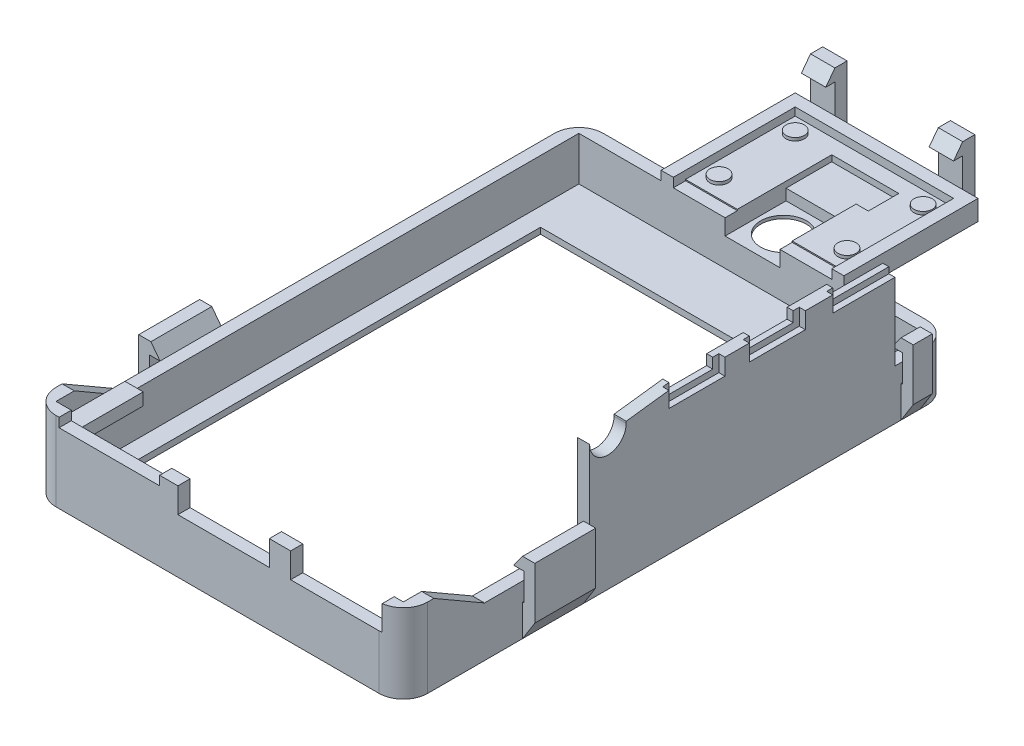
SolidWorks part; units mm, degrees
ref_plane "Płaszczyzna przednia" through (0, 0, 0) normal (0, 0, 1) x (1, 0, 0)
ref_plane "Płaszczyzna górna" through (0, 0, 0) normal (0, 1, 0) x (1, 0, 0)
ref_plane "Płaszczyzna prawa" through (0, 0, 0) normal (1, 0, 0) x (0, 0, -1)
sketch "Szkic2" plane through (0, 0, 0) normal (0, 1, 0) x (1, 0, 0)
  line L0 (-30.5, -40.9) -> (-25.5, -40.9) construction
  line L1 (-26.5, 44.9) -> (26.5, 44.9)
  line L2 (-30.5, 40.9) -> (-30.5, -40.9)
  line L3 (-26.5, -44.9) -> (26.5, -44.9)
  line L4 (30.5, 40.9) -> (30.5, -40.9)
  line L5 (-30.5, 44.9) -> (30.5, -44.9) construction
  line L6 (-30.5, -44.9) -> (30.5, 44.9) construction
  line L7 (-25.5, -41.9) -> (25.5, -41.9)
  line L8 (-25.5, -41.9) -> (-25.5, 33.6)
  line L9 (-25.5, 33.6) -> (25.5, 33.6)
  line L10 (25.5, -41.9) -> (25.5, 33.6)
  line L11 (25.5, -40.9) -> (30.5, -40.9) construction
  arc A0 (-30.5, -40.9) -> (-26.5, -44.9) centre (-26.5, -40.9) ccw
  arc A1 (26.5, -44.9) -> (30.5, -40.9) centre (26.5, -40.9) ccw
  arc A2 (26.5, 44.9) -> (30.5, 40.9) centre (26.5, 40.9) cw
  arc A3 (-26.5, 44.9) -> (-30.5, 40.9) centre (-26.5, 40.9) ccw
  point P0 (0, 0)
  point P18 (0, 0)
  dimension "D3" = 4
  dimension "D1" = 89.8
  dimension "D2" = 61
  dimension "D4" = 51
  dimension "D5" = 3
  dimension "D6" = 75.5
extrude "Dodanie-wyciągnięcie1" add sketch "Szkic2" along normal blind 1
sketch "Szkic3" plane through (0, 1, 0) normal (0, 1, 0) x (1, 0, 0)
  line L1 (-28.5, 42.9) -> (28.5, 42.9)
  line L2 (-28.5, 42.9) -> (-28.5, -42.9)
  line L3 (-28.5, -42.9) -> (28.5, -42.9)
  line L4 (28.5, 42.9) -> (28.5, -42.9)
  line L8 (-26.5, -44.9) -> (26.5, -44.9)
  line L9 (30.5, -40.9) -> (30.5, 40.9)
  line L10 (26.5, 44.9) -> (-26.5, 44.9)
  line L11 (-30.5, 40.9) -> (-30.5, -40.9)
  line L12 (-26.5, -44.9) -> (26.5, -44.9)
  line L13 (30.5, -40.9) -> (30.5, 40.9)
  line L14 (26.5, 44.9) -> (-26.5, 44.9)
  line L15 (-30.5, 40.9) -> (-30.5, -40.9)
  arc A4 (-30.5, -40.9) -> (-26.5, -44.9) centre (-26.5, -40.9) ccw
  arc A5 (26.5, -44.9) -> (30.5, -40.9) centre (26.5, -40.9) ccw
  arc A6 (30.5, 40.9) -> (26.5, 44.9) centre (26.5, 40.9) ccw
  arc A7 (-26.5, 44.9) -> (-30.5, 40.9) centre (-26.5, 40.9) ccw
  arc A8 (-30.5, -40.9) -> (-26.5, -44.9) centre (-26.5, -40.9) ccw
  arc A9 (26.5, -44.9) -> (30.5, -40.9) centre (26.5, -40.9) ccw
  arc A10 (30.5, 40.9) -> (26.5, 44.9) centre (26.5, 40.9) ccw
  arc A11 (-26.5, 44.9) -> (-30.5, 40.9) centre (-26.5, 40.9) ccw
  dimension "D2" = 2
  dimension "D3" = 2
  dimension "D4" = 2
  dimension "D5" = 2
  dimension "D1" = 0
extrude "Dodanie-wyciągnięcie2" add sketch "Szkic3" along normal blind 7.2
sketch "Szkic4" plane through (0, 8.2, 0) normal (0, 1, 0) x (1, 0, 0)
  line L0 (30.5, -40.9) -> (30.5, 40.9) construction
  line L1 (28.5, -42.9) -> (28.5, 42.9) construction
  line L2 (30.5, -14.33) -> (30.5, 35.77)
  line L3 (28.5, -14.33) -> (28.5, 35.77)
  line L4 (28.5, 35.77) -> (30.5, 35.77)
  line L5 (28.5, -14.33) -> (30.5, -14.33)
  line L6 (26.5, 44.9) -> (-26.5, 44.9) construction
  dimension "D1" = 50.1
  dimension "D2" = 9.13
extrude "Dodanie-wyciągnięcie3" add sketch "Szkic4" along normal blind 8
sketch "Szkic5" plane through (0, 0, 0) normal (0, -1, 0) x (1, 0, 0)
  line L0 (4.5, -44.9) -> (4.5, -42.9)
  line L1 (26.5, -44.9) -> (-26.5, -44.9) construction
  line L2 (4.5, -42.9) -> (-4.5, -42.9)
  line L3 (-4.5, -42.9) -> (-4.5, -44.9)
  line L4 (-4.5, -44.9) -> (4.5, -44.9)
  line L5 (-30.5, -40.9) -> (-30.5, -49.1859) construction
  line L6 (-4.5, -44.9) -> (-30.5, -44.9) construction
  line L7 (30.5, -40.9) -> (30.5, -54.2509) construction
  line L8 (4.5, -44.9) -> (30.5, -44.9) construction
  line L9 (30.5, 40.9) -> (30.5, -40.9) construction
  line L10 (-30.5, -40.9) -> (-30.5, 40.9) construction
  dimension "D1" = 9
  dimension "D2" = 2
extrude "Wytnij-wyciągnięcie1" cut sketch "Szkic5" against normal up to surface (8.2 mm away) up to face at (7.375, 8.2, -2.68)
sketch "Szkic8" plane through (0, 8.2, 0) normal (0, 1, 0) x (1, 0, 0)
  line L0 (30.5, -40.9) -> (30.5, -14.33) construction
  line L1 (28.5, -42.9) -> (28.5, -14.33) construction
  line L2 (-28.5, -42.9) -> (28.5, -42.9) construction
  line L3 (-28.5, 42.9) -> (-28.5, -42.9) construction
  line L4 (-30.5, 40.9) -> (-30.5, -40.9) construction
  line L5 (-26.5, -44.9) -> (26.5, -44.9) construction
  line L6 (30.5, -40.9) -> (30.5, -31.59)
  line L7 (28.5, -42.9) -> (28.5, -31.59)
  line L8 (-28.5, -42.9) -> (28.5, -42.9)
  line L9 (-28.5, -31.59) -> (-28.5, -42.9)
  line L10 (-30.5, -31.59) -> (-30.5, -40.9)
  line L11 (-26.5, -44.9) -> (26.5, -44.9)
  line L12 (30.5, -31.59) -> (28.5, -31.59)
  line L13 (-28.5, -31.59) -> (-30.5, -31.59)
  arc A0 (26.5, -44.9) -> (30.5, -40.9) centre (26.5, -40.9) ccw construction
  arc A1 (-30.5, -40.9) -> (-26.5, -44.9) centre (-26.5, -40.9) ccw construction
  arc A2 (26.5, -44.9) -> (30.5, -40.9) centre (26.5, -40.9) ccw
  arc A3 (-30.5, -40.9) -> (-26.5, -44.9) centre (-26.5, -40.9) ccw
  dimension "D1" = 13.31
extrude "Dodanie-wyciągnięcie5" add sketch "Szkic8" along normal blind 4.8
sketch "Szkic9" plane through (-30.5, 0, 0) normal (-1, 0, 0) x (0, 0, 1)
  line L0 (31.59, 13) -> (40.9, 13) construction
  line L1 (31.59, 13) -> (31.59, 8.2) construction
  line L2 (31.59, 13) -> (39.9038, 13)
  line L3 (31.59, 13) -> (31.59, 8.2)
  line L4 (31.59, 8.2) -> (39.9038, 13)
  line L5 (-40.9, 8.2) -> (31.59, 8.2) construction
  dimension "D1" = 150
extrude "Wytnij-wyciągnięcie3" cut sketch "Szkic9" against normal through all
sketch "Szkic10" plane through (0, 0, 44.9) normal (0, 0, 1) x (1, 0, 0)
  line L0 (-26, 13) -> (-26, 11.5)
  line L1 (-26.5, 13) -> (26.5, 13) construction
  line L2 (-26, 11.5) -> (-9.5, 11.5)
  line L3 (-9.5, 11.5) -> (-9.5, 13)
  line L4 (-6.5, 13) -> (-6.5, 8.9)
  line L5 (-6.5, 8.9) -> (8.5, 8.9)
  line L6 (8.5, 8.9) -> (8.5, 13)
  line L7 (12, 13) -> (12, 8.9)
  line L8 (12, 8.9) -> (27, 8.9)
  line L9 (27, 8.9) -> (27, 13)
  line L10 (27, 13) -> (12, 13)
  line L11 (8.5, 13) -> (-6.5, 13)
  line L12 (-9.5, 13) -> (-26, 13)
  line L13 (-30.5, 13) -> (-30.5, 0) construction
  point P16 (-9.5, 11.5)
  point P17 (-9.5, 13)
  point P18 (-26, 13)
  point P19 (-26, 11.5)
  point P20 (-6.5, 13)
  point P21 (-6.5, 8.9)
  point P22 (8.5, 8.9)
  dimension "D1" = 15
  dimension "D2" = 3.5
  dimension "D3" = 3
  dimension "D4" = 16.5
  dimension "D5" = 4.5
  dimension "D6" = 1.5
  dimension "D7" = 4.1
extrude "Wytnij-wyciągnięcie4" cut sketch "Szkic10" along direction (0, 0, -1) on the side against the normal up to surface (2 mm away) up to face at (0, 7, 42.9)
sketch "Szkic12" plane through (30.5, 0, 0) normal (1, 0, 0) x (0, 0, -1)
  line L0 (-14.33, 16.2) -> (-14.33, 22.1)
  line L2 (-14.33, 16.2) -> (35.77, 16.2) construction
  line L3 (-0.33, 23.4) -> (-0.33, 21.7)
  line L4 (-0.33, 21.7) -> (6.87, 21.7)
  line L5 (6.87, 21.7) -> (6.87, 23.4)
  line L6 (6.87, 23.4) -> (12.87, 23.4)
  line L7 (12.87, 23.4) -> (12.87, 21.7)
  line L8 (12.87, 21.7) -> (20.07, 21.7)
  line L9 (20.07, 21.7) -> (20.07, 23.4)
  line L10 (20.07, 23.4) -> (26.57, 23.4)
  line L11 (26.57, 23.4) -> (26.57, 21.8)
  line L12 (26.57, 21.8) -> (35.77, 21.8)
  line L13 (-0.33, 23.4) -> (6.87, 23.4) construction
  line L14 (-14.33, 16.2) -> (35.77, 16.2)
  line L15 (35.77, 21.8) -> (35.77, 16.2)
  line L16 (-14.33, 22.1) -> (-11.33, 22.1) construction
  line L17 (-0.33, 23.4) -> (-8.33, 22.4)
  line L18 (-8.33, 22.4) -> (-8.33, 22.1)
  arc A0 (-14.33, 22.1) -> (-8.33, 22.1) centre (-11.33, 22.1) ccw
  dimension "D2" = 6
  dimension "D1" = 6.2
  dimension "D3" = 7.2
  dimension "D4" = 8
  dimension "D5" = 9.2
  dimension "D6" = 6.5
  dimension "D7" = 6
  dimension "D8" = 5.6
  dimension "D9" = 5.5
  dimension "D10" = 0.3
extrude "Dodanie-wyciągnięcie7" add sketch "Szkic12" against normal up to surface (2 mm away) up to face at (28.5, 9.32, 2.8614)
sketch "Szkic11" plane through (-28.5, 0, 0) normal (1, 0, 0) x (0, 0, -1)
  line L1 (-31.59, 10.2) -> (-31.59, 8.2)
  line L2 (-31.59, 8.2) -> (-42.9, 8.2)
  line L3 (-42.9, 13) -> (-42.9, 1) construction
  line L8 (-42.9, 10.2) -> (-42.9, 8.2)
  line L9 (-42.9, 10.2) -> (-31.59, 10.2)
  dimension "D1" = 2
extrude "Dodanie-wyciągnięcie6" add sketch "Szkic11" along normal blind 3
sketch "Szkic13" plane through (0, 0, -44.9) normal (0, 0, -1) x (-1, 0, 0)
  line L0 (15, 8.2) -> (15, 9.7)
  line L1 (4.5, 8.2) -> (26.5, 8.2) construction
  line L2 (15, 9.7) -> (13, 9.7)
  line L3 (13, 9.7) -> (13, 8.4)
  line L4 (13, 8.4) -> (4.5, 8.4)
  line L5 (-13, 8.4) -> (-13, 9.7)
  line L6 (-13, 9.7) -> (-15, 9.7)
  line L7 (-15, 9.7) -> (-15, 8.2)
  line L8 (-26.5, 8.2) -> (-4.5, 8.2) construction
  line L9 (4.5, 8.2) -> (15, 8.2) construction
  line L10 (-4.5, 8.2) -> (-15, 8.2) construction
  line L11 (4.5, 8.4) -> (4.5, 8.2)
  line L12 (-13, 8.4) -> (-4.5, 8.4)
  line L13 (-4.5, 8.4) -> (-4.5, 8.2)
  line L14 (15, 8.2) -> (15, 6.4)
  line L15 (15, 6.4) -> (4.5, 6.4)
  line L16 (4.5, 8.2) -> (4.5, 0) construction
  line L17 (4.5, 6.4) -> (4.5, 8.2)
  line L18 (-4.5, 8.2) -> (-4.5, 6.4)
  line L19 (-4.5, 8.2) -> (-4.5, 0) construction
  line L20 (-4.5, 6.4) -> (-15, 6.4)
  line L21 (-15, 6.4) -> (-15, 8.2)
  dimension "D1" = 30
  dimension "D2" = 2
  dimension "D3" = 1.5
  dimension "D4" = 2
  dimension "D5" = 0.2
extrude "Dodanie-wyciągnięcie8" add sketch "Szkic13" along normal blind 20
sketch "Szkic14" plane through (-13, 0, 0) normal (1, 0, 0) x (0, 0, -1)
  line L0 (64.9, 8.4) -> (44.9, 8.4) construction
  line L1 (64.9, 9.7) -> (62.9, 9.7)
  line L2 (64.9, 9.7) -> (64.9, 8.4)
  line L3 (64.9, 8.4) -> (62.9, 8.4)
  line L4 (62.9, 9.7) -> (62.9, 8.4)
  dimension "D1" = 2
extrude "Dodanie-wyciągnięcie9" add sketch "Szkic14" along normal up to surface (8.5 mm away) up to face at (-4.5, 5.2222, -48.6778)
sketch "Szkic15" plane through (13, 0, 0) normal (-1, 0, 0) x (0, 0, 1)
  line L0 (-64.9, 8.4) -> (-44.9, 8.4) construction
  line L1 (-64.9, 9.7) -> (-62.9, 9.7)
  line L2 (-64.9, 9.7) -> (-64.9, 8.4)
  line L3 (-64.9, 8.4) -> (-62.9, 8.4)
  line L4 (-62.9, 9.7) -> (-62.9, 8.4)
  dimension "D1" = 2
extrude "Dodanie-wyciągnięcie10" add sketch "Szkic15" along normal up to surface (8.5 mm away) up to face at (4.5, 5.2222, -48.6778)
sketch "Szkic16" plane through (0, 8.4, 0) normal (0, 1, 0) x (1, 0, 0)
  line L0 (-10.5, 60.4) -> (-10.5, 62.9) construction
  line L1 (-4.5, 62.9) -> (-13, 62.9) construction
  line L2 (-10.5, 60.4) -> (-13, 60.4) construction
  line L3 (-13, 62.9) -> (-13, 44.9) construction
  line L4 (10.5, 60.4) -> (10.5, 62.9) construction
  line L5 (4.5, 62.9) -> (13, 62.9) construction
  line L6 (10.5, 60.4) -> (13, 60.4) construction
  line L8 (-10.5, 47.9) -> (-10.5, 60.4) construction
  line L9 (10.5, 47.9) -> (10.5, 60.4) construction
  line L10 (-10.5, 47.9) -> (10.5, 47.9) construction
  line L11 (-10.5, 60.4) -> (10.5, 60.4) construction
  line L12 (13, 62.9) -> (13, 44.9) construction
  circle A0 centre (-10.5, 60.4) radius 1.5
  circle A1 centre (-10.5, 47.9) radius 1.5
  circle A2 centre (10.5, 60.4) radius 1.5
  circle A3 centre (10.5, 47.9) radius 1.5
  dimension "D1" = 3
  dimension "D2" = 2.5
  dimension "D3" = 2.5
  dimension "D4" = 12.5
extrude "Dodanie-wyciągnięcie11" add sketch "Szkic16" along normal blind 0.5
sketch "Szkic18" plane through (0, 8.4, 0) normal (0, 1, 0) x (1, 0, 0)
  line L0 (4.5, 60.4) -> (6.5, 60.4)
  line L1 (4.5, 62.9) -> (4.5, 44.9) construction
  line L2 (6.5, 60.4) -> (6.5, 55.4)
  line L3 (6.5, 55.4) -> (4.5, 55.4)
  line L4 (4.5, 55.4) -> (4.5, 60.4)
  line L5 (4.5, 62.9) -> (13, 62.9) construction
  dimension "D1" = 2
  dimension "D2" = 5
  dimension "D3" = 2.5
extrude "Wytnij-wyciągnięcie6" cut sketch "Szkic18" against normal blind 1
sketch "Szkic20" plane through (0, 6.4, 0) normal (0, -1, 0) x (1, 0, 0)
  line L0 (4.5, -60.4) -> (-4.5, -60.4)
  line L1 (4.5, -64.9) -> (4.5, -44.9) construction
  line L2 (4.5, -55.4) -> (-4.5, -55.4)
  line L4 (-4.5, -64.9) -> (-4.5, -44.9) construction
  line L5 (4.5, -60.4) -> (4.5, -55.4)
  line L6 (-4.5, -60.4) -> (-4.5, -55.4)
  dimension "D1" = 5
extrude "Dodanie-wyciągnięcie12" add sketch "Szkic20" against normal up to surface (1 mm away) up to face at (5.5, 7.4, -57.9)
sketch "Szkic21" plane through (0, 6.4, 0) normal (0, -1, 0) x (-1, 0, 0)
  line L0 (4.5, 44.9) -> (4.5, 52.9)
  line L1 (4.5, 55.4) -> (4.5, 44.9) construction
  line L2 (4.5, 52.9) -> (-4.5, 52.9)
  line L3 (-4.5, 55.4) -> (-4.5, 44.9) construction
  line L4 (-4.5, 52.9) -> (-4.5, 44.9)
  line L5 (-4.5, 44.9) -> (-5.5, 44.9)
  line L6 (-15, 44.9) -> (-4.5, 44.9) construction
  line L7 (-5.5, 44.9) -> (-5.5, 53.9)
  line L8 (-5.5, 53.9) -> (5.5, 53.9)
  line L9 (5.5, 53.9) -> (5.5, 44.9)
  line L10 (4.5, 44.9) -> (15, 44.9) construction
  line L11 (5.5, 44.9) -> (4.5, 44.9) construction
  line L13 (0, 53.9) -> (0, 52.9) construction
  line L26 (4.5, 44.9) -> (15, 44.9)
  line L27 (15, 44.9) -> (15, 64.9)
  line L28 (15, 64.9) -> (4.5, 64.9)
  line L29 (4.5, 64.9) -> (4.5, 60.4)
  line L30 (4.5, 60.4) -> (-4.5, 60.4)
  line L31 (-4.5, 60.4) -> (-4.5, 64.9)
  line L32 (-4.5, 64.9) -> (-15, 64.9)
  line L33 (-15, 64.9) -> (-15, 44.9)
  line L34 (-15, 44.9) -> (-4.5, 44.9)
  line L35 (-4.5, 44.9) -> (-4.5, 55.4)
  line L36 (-4.5, 55.4) -> (4.5, 55.4)
  line L37 (4.5, 55.4) -> (4.5, 44.9)
  line L38 (4.5, 44.9) -> (5.5, 44.9)
  dimension "D1" = 8
  dimension "D2" = 1
  dimension "D3" = 0
extrude "Dodanie-wyciągnięcie13" add sketch "Szkic21" along normal blind 0.7
sketch "Szkic22" plane through (0, 5.7, 0) normal (0, -1, 0) x (1, 0, 0)
  line L0 (-4.5, -52.9) -> (-4.5, -53.9)
  line L1 (-5.5, -53.9) -> (5.5, -53.9) construction
  line L2 (-4.5, -52.9) -> (4.5, -52.9)
  line L3 (4.5, -52.9) -> (4.5, -53.9)
  line L4 (4.5, -53.9) -> (-4.5, -53.9)
extrude "Wytnij-wyciągnięcie7" cut sketch "Szkic22" against normal blind 0.7
sketch "Szkic23" plane through (-4.5, 0, 0) normal (1, 0, 0) x (0, 0, -1)
  line L0 (60.4, 7.4) -> (60.4, 8.4)
  line L1 (55.4, 7.4) -> (52.9, 7.4)
  line L2 (52.9, 7.4) -> (52.9, 5.7)
  line L17 (44.9, 0) -> (44.9, 5.7)
  line L18 (44.9, 5.7) -> (53.9, 5.7)
  line L19 (53.9, 5.7) -> (53.9, 6.4)
  line L20 (53.9, 6.4) -> (55.4, 6.4)
  line L21 (55.4, 6.4) -> (55.4, 7.4)
  line L22 (55.4, 7.4) -> (60.4, 7.4)
  line L23 (60.4, 7.4) -> (60.4, 6.4)
  line L24 (60.4, 6.4) -> (64.9, 6.4)
  line L25 (64.9, 6.4) -> (64.9, 9.7)
  line L26 (64.9, 9.7) -> (62.9, 9.7)
  line L27 (62.9, 9.7) -> (62.9, 8.4)
  line L28 (62.9, 8.4) -> (44.9, 8.4)
  line L29 (44.9, 8.4) -> (44.9, 8.2)
  line L30 (44.9, 8.2) -> (42.9, 8.2)
  line L31 (42.9, 8.2) -> (42.9, 1)
  line L32 (42.9, 1) -> (42.9, 0)
  line L33 (42.9, 0) -> (44.9, 0)
  line L35 (52.9, 5.7) -> (53.9, 5.7)
  line L36 (53.9, 5.7) -> (53.9, 6.4)
  line L37 (53.9, 6.4) -> (55.4, 6.4)
  line L38 (55.4, 6.4) -> (55.4, 7.4)
  line L40 (60.4, 7.4) -> (60.4, 6.4)
  line L41 (60.4, 6.4) -> (64.9, 6.4)
  line L42 (64.9, 6.4) -> (64.9, 9.7)
  line L43 (64.9, 9.7) -> (62.9, 9.7)
  line L44 (62.9, 9.7) -> (62.9, 8.4)
  line L45 (62.9, 8.4) -> (60.4, 8.4)
  point P8 (53.9, 6.05)
  dimension "D2" = 1
  dimension "D1" = 0
extrude "Dodanie-wyciągnięcie14" add sketch "Szkic23" along normal up to surface (9 mm away) up to face at (4.5, 5.4833, -48.525)
sketch "Szkic24" plane through (0, 0, -44.9) normal (0, 0, 1) x (1, 0, 0)
  line L0 (13, 8.4) -> (13, 8.2)
  line L1 (-13, 8.4) -> (-13, 8.2)
  line L6 (-15, 9.7) -> (-15, 8.2)
  line L7 (-15, 8.2) -> (-4.5, 8.2)
  line L8 (-4.5, 8.2) -> (-4.5, 8.4)
  line L9 (-4.5, 8.4) -> (-13, 8.4)
  line L10 (-13, 8.4) -> (-13, 9.7)
  line L11 (-13, 9.7) -> (-15, 9.7)
  line L12 (-15, 9.7) -> (-15, 8.2)
  line L13 (-15, 8.2) -> (-13, 8.2)
  line L16 (-13, 8.4) -> (-13, 9.7)
  line L17 (-13, 9.7) -> (-15, 9.7)
  line L18 (4.5, 8.4) -> (4.5, 8.2)
  line L19 (4.5, 8.2) -> (15, 8.2)
  line L20 (15, 8.2) -> (15, 9.7)
  line L21 (15, 9.7) -> (13, 9.7)
  line L22 (13, 9.7) -> (13, 8.4)
  line L25 (13, 8.2) -> (15, 8.2)
  line L26 (15, 8.2) -> (15, 9.7)
  line L28 (13, 9.7) -> (13, 8.4)
  line L32 (15, 9.7) -> (13, 9.7)
  line L33 (13, 8.4) -> (4.5, 8.4)
  dimension "D1" = 0
  dimension "D2" = 0
extrude "Dodanie-wyciągnięcie15" add sketch "Szkic24" along normal up to surface (2 mm away) up to face at (16.5, 4.6, -42.9)
sketch "Szkic25" plane through (30.5, 0, 0) normal (1, 0, 0) x (0, 0, -1)
  line L0 (-31.59, 8.2) -> (-14.33, 8.2) construction
  line L1 (-15.33, 8.2) -> (-25.33, 8.2)
  line L2 (-15.33, 8.2) -> (-15.33, 6.2)
  line L3 (-15.33, 6.2) -> (-25.33, 6.2)
  line L4 (-25.33, 8.2) -> (-25.33, 6.2)
  line L5 (-14.33, 22.1) -> (-14.33, 8.2) construction
  dimension "D1" = 1
  dimension "D2" = 10
  dimension "D3" = 2
extrude "Dodanie-wyciągnięcie16" add sketch "Szkic25" along normal blind 2
sketch "Szkic26" plane through (0, 8.2, 0) normal (0, 1, 0) x (1, 0, 0)
  line L1 (32.5, -15.33) -> (30.5, -15.33)
  line L2 (32.5, -15.33) -> (32.5, -25.33)
  line L3 (32.5, -25.33) -> (30.5, -25.33)
  line L4 (30.5, -15.33) -> (30.5, -25.33)
extrude "Dodanie-wyciągnięcie17" add sketch "Szkic26" along normal blind 3.5
sketch "Szkic27" plane through (0, 0, 25.33) normal (0, 0, 1) x (1, 0, 0)
  line L0 (30.5, 11.7) -> (30.5, 9.7)
  line L1 (30.5, 11.7) -> (30.5, 8.2) construction
  line L2 (30.5, 9.7) -> (29, 9.7)
  line L3 (29, 9.7) -> (30.5, 11.7)
  line L4 (30.5, 8.2) -> (28.5, 8.2) construction
  dimension "D1" = 1.5
  dimension "D2" = 1.5
extrude "Dodanie-wyciągnięcie18" add sketch "Szkic27" against normal up to surface (10 mm away) up to face at (31.3, 8.8, 15.33)
sketch "Szkic28" plane through (30.5, 0, 0) normal (1, 0, 0) x (0, 0, -1)
  line L0 (-25.33, 11.7) -> (-15.33, 11.7) construction
  line L1 (39.9, 6.2) -> (36.77, 6.2)
  line L2 (39.9, 6.2) -> (39.9, 11.7)
  line L3 (39.9, 11.7) -> (36.77, 11.7)
  line L4 (36.77, 6.2) -> (36.77, 11.7)
  line L5 (-25.33, 6.2) -> (-15.33, 6.2) construction
  line L6 (35.77, 21.8) -> (35.77, 8.2) construction
  line L7 (40.9, 8.2) -> (40.9, 0) construction
  dimension "D1" = 1
  dimension "D2" = 1
extrude "Dodanie-wyciągnięcie19" add sketch "Szkic28" along normal blind 1
sketch "Szkic29" plane through (0, 0, -39.9) normal (0, 0, -1) x (-1, 0, 0)
  line L0 (-30.5, 11.7) -> (-30.5, 9.7)
  line L7 (-30.5, 6.2) -> (-30.5, 8.2)
  line L8 (-30.5, 8.2) -> (-30.5, 9.7)
  line L9 (-30.5, 9.7) -> (-29, 9.7)
  line L10 (-29, 9.7) -> (-30.5, 11.7)
  line L11 (-30.5, 11.7) -> (-32.5, 11.7)
  line L12 (-32.5, 11.7) -> (-32.5, 6.2)
  line L13 (-32.5, 6.2) -> (-30.5, 6.2)
  line L16 (-30.5, 9.7) -> (-29, 9.7)
  line L17 (-29, 9.7) -> (-30.5, 11.7)
  dimension "D1" = 0
extrude "Dodanie-wyciągnięcie20" add sketch "Szkic29" against normal up to surface (3.13 mm away) up to face at (30.9, 8.8, -36.77)
sketch "Szkic30" plane through (0, 0, -64.9) normal (0, 0, -1) x (-1, 0, 0)
  line L0 (-15, 6.4) -> (15, 6.4) construction
  line L1 (12.4832, 6.4) -> (8.4832, 6.4)
  line L2 (12.4832, 6.4) -> (12.4832, 16.5)
  line L3 (12.4832, 16.5) -> (8.4832, 16.5)
  line L4 (8.4832, 6.4) -> (8.4832, 16.5)
  line L5 (-8.4832, 6.4) -> (-12.4832, 6.4)
  line L6 (-8.4832, 6.4) -> (-8.4832, 16.5)
  line L7 (-8.4832, 16.5) -> (-12.4832, 16.5)
  line L8 (-12.4832, 6.4) -> (-12.4832, 16.5)
  line L9 (12.4832, 6.4) -> (15, 6.4) construction
  line L10 (-12.4832, 6.4) -> (-15, 6.4) construction
  line L11 (15, 9.7) -> (-15, 9.7) construction
  dimension "D1" = 4
  dimension "D2" = 6.8
extrude "Dodanie-wyciągnięcie21" add sketch "Szkic30" along normal blind 2
sketch "Szkic32" plane through (12.4832, 0, 0) normal (1, 0, 0) x (0, 0, -1)
  line L0 (64.9, 16.5) -> (63.4, 14.5)
  line L1 (63.4, 14.5) -> (64.9, 14.5)
  line L2 (64.9, 16.5) -> (64.9, 9.7) construction
  line L3 (64.9, 14.5) -> (64.9, 16.5)
  dimension "D1" = 2
  dimension "D2" = 1.5
extrude "Dodanie-wyciągnięcie22" add sketch "Szkic32" against normal up to surface (24.9664 mm away) up to face at (-12.4832, 11.1, -65.7)
sketch "Szkic33" plane through (0, 0, -64.9) normal (0, 0, -1) x (-1, 0, 0)
  line L4 (8.4832, 14.5) -> (8.4832, 16.5)
  line L5 (8.4832, 16.5) -> (-8.4832, 16.5)
  line L6 (-8.4832, 16.5) -> (-8.4832, 14.5)
  line L7 (-8.4832, 14.5) -> (8.4832, 14.5)
  line L8 (8.4832, 14.5) -> (8.4832, 16.5)
  line L9 (8.4832, 16.5) -> (-8.4832, 16.5)
  line L10 (-8.4832, 16.5) -> (-8.4832, 14.5)
  line L11 (-8.4832, 14.5) -> (8.4832, 14.5)
  dimension "D1" = 0
extrude "Wytnij-wyciągnięcie8" cut sketch "Szkic33" against normal up to surface up to face at (0, 15.8333, -64.4)
sketch "Szkic34" plane through (0, 6.2, 0) normal (0, -1, 0) x (1, 0, 0)
  line L4 (30.5, 25.33) -> (30.5, 15.33)
  line L5 (30.5, 15.33) -> (32.5, 15.33)
  line L6 (32.5, 15.33) -> (32.5, 25.33)
  line L7 (32.5, 25.33) -> (30.5, 25.33)
  line L8 (30.5, 25.33) -> (30.5, 15.33)
  line L9 (30.5, 15.33) -> (32.5, 15.33)
  line L10 (32.5, 15.33) -> (32.5, 25.33)
  line L11 (32.5, 25.33) -> (30.5, 25.33)
  line L12 (30.5, -36.77) -> (30.5, -39.9)
  line L13 (30.5, -39.9) -> (31.5, -39.9)
  line L14 (31.5, -39.9) -> (31.5, -36.77)
  line L15 (31.5, -36.77) -> (30.5, -36.77)
  line L16 (30.5, -36.77) -> (30.5, -39.9)
  line L17 (30.5, -39.9) -> (31.5, -39.9)
  line L18 (31.5, -39.9) -> (31.5, -36.77)
  line L19 (31.5, -36.77) -> (30.5, -36.77)
  dimension "D1" = 0
  dimension "D2" = 0
extrude "Dodanie-wyciągnięcie23" add sketch "Szkic34" along normal blind 3
sketch "Szkic35" plane through (0, 0, -39.9) normal (0, 0, -1) x (-1, 0, 0)
  line L0 (-30.5, 9.7) -> (-30.7, 9.7)
  line L1 (-30.7, 9.7) -> (-30.7, 5.2)
  line L2 (-30.7, 5.2) -> (-30.5, 5.2)
  line L3 (-30.5, 3.2) -> (-31.5, 3.2) construction
  line L7 (-30.5, 3.2) -> (-30.5, 8.2)
  line L8 (-30.5, 8.2) -> (-30.5, 9.7)
  line L9 (-30.5, 9.7) -> (-29, 9.7)
  line L10 (-29, 9.7) -> (-30.5, 11.7)
  line L11 (-30.5, 11.7) -> (-31.5, 11.7)
  line L12 (-31.5, 11.7) -> (-31.5, 3.2)
  line L13 (-31.5, 3.2) -> (-30.5, 3.2)
  line L14 (-30.5, 5.2) -> (-30.5, 8.2)
  line L15 (-30.5, 8.2) -> (-30.5, 9.7)
  dimension "D2" = 0.2
  dimension "D3" = 2
  dimension "D1" = 0
extrude "Wytnij-wyciągnięcie9" cut sketch "Szkic35" against normal through all
sketch "Szkic36" plane through (31.5, 0, 0) normal (1, 0, 0) x (0, 0, -1)
  line L4 (39.9, 3.2) -> (39.9, 11.7)
  line L5 (39.9, 11.7) -> (36.77, 11.7)
  line L6 (36.77, 11.7) -> (36.77, 3.2)
  line L7 (36.77, 3.2) -> (39.9, 3.2)
  line L8 (39.9, 3.2) -> (39.9, 11.7)
  line L9 (39.9, 11.7) -> (36.77, 11.7)
  line L10 (36.77, 11.7) -> (36.77, 3.2)
  line L11 (36.77, 3.2) -> (39.9, 3.2)
  dimension "D1" = 0
extrude "Dodanie-wyciągnięcie24" add sketch "Szkic36" along normal up to surface (1 mm away) up to face at (32.5, 7.45, 20.33)
sketch "Szkic38" plane through (0, 5.7, 0) normal (0, -1, 0) x (1, 0, 0)
  line L8 (-5.5, -53.9) -> (5.5, -53.9)
  line L9 (5.5, -53.9) -> (5.5, -44.9)
  line L10 (5.5, -44.9) -> (4.5, -44.9)
  line L11 (4.5, -44.9) -> (4.5, -52.9)
  line L12 (4.5, -52.9) -> (-4.5, -52.9)
  line L13 (-4.5, -52.9) -> (-4.5, -44.9)
  line L14 (-4.5, -44.9) -> (-5.5, -44.9)
  line L15 (-5.5, -44.9) -> (-5.5, -53.9)
  line L16 (-5.5, -53.9) -> (5.5, -53.9)
  line L17 (5.5, -53.9) -> (5.5, -44.9)
  line L18 (5.5, -44.9) -> (4.5, -44.9)
  line L19 (4.5, -44.9) -> (4.5, -52.9)
  line L20 (4.5, -52.9) -> (-4.5, -52.9)
  line L21 (-4.5, -52.9) -> (-4.5, -44.9)
  line L22 (-4.5, -44.9) -> (-5.5, -44.9)
  line L23 (-5.5, -44.9) -> (-5.5, -53.9)
  dimension "D1" = 0
extrude "Dodanie-wyciągnięcie25" add sketch "Szkic38" along normal blind 0.6
sketch "Szkic39" plane through (-4.5, 0, 0) normal (1, 0, 0) x (0, 0, -1)
  line L0 (42.9, 5.1) -> (42.9, 5.6)
  line L1 (42.9, 5.6) -> (52.9, 5.6)
  line L2 (52.9, 7.4) -> (52.9, 5.1) construction
  line L3 (52.9, 5.6) -> (52.9, 5.1)
  line L4 (52.9, 5.1) -> (42.9, 5.1)
  line L5 (42.9, 8.2) -> (42.9, 1) construction
  dimension "D1" = 0.5
extrude "Dodanie-wyciągnięcie26" add sketch "Szkic39" along normal up to surface (9 mm away) up to face at (4.5, 5.3818, -47.7182)
sketch "Szkic41" plane through (0, 5.1, 0) normal (0, -1, 0) x (1, 0, 0)
  line L0 (0, -51.75) -> (0, -53.5) construction
  line L1 (0, -53.5) -> (0, -53.9) construction
  line L2 (-5.5, -53.9) -> (5.5, -53.9) construction
  line L3 (-3.75, -48) -> (-5.5, -48) construction
  line L4 (-5.5, -44.9) -> (-5.5, -53.9) construction
  line L5 (3.75, -48) -> (5.5, -48) construction
  line L6 (5.5, -53.9) -> (5.5, -44.9) construction
  circle A0 centre (0, -48) radius 3.75
  dimension "D1" = 7.5
  dimension "D2" = 0.4
extrude "Wytnij-wyciągnięcie10" cut sketch "Szkic41" against normal up to surface (0.5 mm away) up to face at (0, 5.6, -47.9)
mirror "Lustro3" about plane through (0, 0, 0) normal (1, 0, 0) of "Wytnij-wyciągnięcie9", "Dodanie-wyciągnięcie23", "Dodanie-wyciągnięcie16", "Dodanie-wyciągnięcie17", "Dodanie-wyciągnięcie18"
sketch "Szkic42" plane through (-31.5, 0, 0) normal (-1, 0, 0) x (0, 0, 1)
  line L4 (-36.77, 6.2) -> (-39.9, 6.2)
  line L5 (-39.9, 6.2) -> (-39.9, 3.2)
  line L6 (-39.9, 3.2) -> (-36.77, 3.2)
  line L7 (-36.77, 3.2) -> (-36.77, 6.2)
  line L8 (-36.77, 6.2) -> (-39.9, 6.2)
  line L9 (-39.9, 6.2) -> (-39.9, 3.2)
  line L10 (-39.9, 3.2) -> (-36.77, 3.2)
  line L11 (-36.77, 3.2) -> (-36.77, 6.2)
  dimension "D1" = 0
extrude "Wytnij-wyciągnięcie11" cut sketch "Szkic42" against normal up to surface (1 mm away) up to face at (-30.5, 4.2, 20.33)
sketch "Szkic43" plane through (30.5, 0, 0) normal (1, 0, 0) x (0, 0, -1)
  line L0 (35.77, 20.8) -> (25.57, 20.8)
  line L1 (35.77, 21.8) -> (35.77, 8.2) construction
  line L2 (25.57, 20.8) -> (25.57, 23.4)
  line L3 (26.57, 23.4) -> (20.07, 23.4) construction
  line L4 (25.57, 23.4) -> (26.57, 23.4)
  line L5 (26.57, 23.4) -> (26.57, 21.8)
  line L6 (26.57, 21.8) -> (35.77, 21.8)
  line L7 (35.77, 21.8) -> (35.77, 20.8)
  line L8 (21.07, 23.4) -> (21.07, 20.7)
  line L9 (21.07, 20.7) -> (11.87, 20.7)
  line L10 (11.87, 20.7) -> (11.87, 23.4)
  line L11 (12.87, 23.4) -> (6.87, 23.4) construction
  line L12 (11.87, 23.4) -> (12.87, 23.4)
  line L13 (12.87, 23.4) -> (12.87, 21.7)
  line L14 (12.87, 21.7) -> (20.07, 21.7)
  line L15 (20.07, 21.7) -> (20.07, 23.4)
  line L16 (20.07, 23.4) -> (20.07, 21.7) construction
  line L17 (20.07, 23.4) -> (21.07, 23.4)
  line L18 (6.87, 23.4) -> (7.87, 23.4)
  line L19 (7.87, 23.4) -> (7.87, 20.7)
  line L20 (7.87, 20.7) -> (-1.33, 20.7)
  line L21 (-1.33, 20.7) -> (-1.33, 23.275)
  line L22 (-0.33, 23.4) -> (-8.33, 22.4) construction
  line L23 (-1.33, 23.275) -> (-0.33, 23.4)
  line L24 (-0.33, 23.4) -> (-0.33, 21.7)
  line L25 (-0.33, 21.7) -> (6.87, 21.7)
  line L26 (6.87, 21.7) -> (-0.33, 21.7) construction
  line L27 (6.87, 21.7) -> (6.87, 23.4)
  line L28 (-1.33, 23.275) -> (-0.33, 23.275) construction
  dimension "D1" = 1
  dimension "D2" = 1
extrude "Wytnij-wyciągnięcie12" cut sketch "Szkic43" against normal blind 1
sketch "Szkic44" plane through (0, 0, 25.33) normal (0, 0, 1) x (1, 0, 0)
  line L0 (32.5, 3.2) -> (30.5, 3.2)
  line L1 (30.5, 3.2) -> (30.5, 0)
  line L2 (30.5, 0) -> (32.5, 3.2)
  point P5 (0, 0)
  point P6 (0, 0)
  point P7 (30.5, 0)
  point P10 (30.5, 0)
extrude "Dodanie-wyciągnięcie27" add sketch "Szkic44" against normal up to surface (65.23 mm away) up to face at (30.8625, 7.45, -39.9)
sketch "Szkic45" plane through (0, 3.2, 0) normal (0, 1, 0) x (1, 0, 0)
  line L4 (30.5, -15.33) -> (32.5, -15.33)
  line L5 (32.5, -15.33) -> (32.5, 36.77)
  line L6 (32.5, 36.77) -> (30.5, 36.77)
  line L7 (30.5, 36.77) -> (30.5, -15.33)
  line L8 (30.5, -15.33) -> (32.5, -15.33)
  line L9 (32.5, -15.33) -> (32.5, 36.77)
  line L10 (32.5, 36.77) -> (30.5, 36.77)
  line L11 (30.5, 36.77) -> (30.5, -15.33)
  dimension "D1" = 0
extrude "Wytnij-wyciągnięcie13" cut sketch "Szkic45" against normal up to surface up to face at (31.8333, 2.1333, -8.43)
sketch "Szkic46" plane through (0, 0, 15.33) normal (0, 0, -1) x (-1, 0, 0)
  line L0 (32.5, 3.2) -> (30.5, 3.2)
  line L1 (30.5, 3.2) -> (30.5, 0)
  line L2 (30.5, 0) -> (32.5, 3.2)
extrude "Dodanie-wyciągnięcie28" add sketch "Szkic46" against normal up to surface (10 mm away) up to face at (-30.8625, 7.45, 25.33)
sketch "Szkic47" plane through (0, 5.1, 0) normal (0, -1, 0) x (1, 0, 0)
  line L0 (-4.5, -44.9) -> (-2.1101, -44.9)
  line L2 (2.1101, -44.9) -> (4.5, -44.9)
  line L8 (-4.5, -42.9) -> (-4.5, -44.9)
  line L9 (-4.5, -44.9) -> (-5.5, -44.9)
  line L10 (-5.5, -44.9) -> (-5.5, -53.9)
  line L11 (-5.5, -53.9) -> (5.5, -53.9)
  line L12 (5.5, -53.9) -> (5.5, -44.9)
  line L13 (5.5, -44.9) -> (4.5, -44.9)
  line L14 (4.5, -44.9) -> (4.5, -42.9)
  line L15 (4.5, -42.9) -> (-4.5, -42.9)
  line L16 (-4.5, -42.9) -> (-4.5, -44.9)
  line L22 (4.5, -44.9) -> (4.5, -42.9)
  line L23 (4.5, -42.9) -> (-4.5, -42.9)
  circle A0 centre (0, -48) radius 3.75 construction
  arc A1 (2.1101, -44.9) -> (-2.1101, -44.9) centre (0, -48) ccw
  dimension "D1" = 0
extrude "Dodanie-wyciągnięcie29" add sketch "Szkic47" along normal up to surface (5.1 mm away) up to face at (3.3889, 0, -9.4972)
